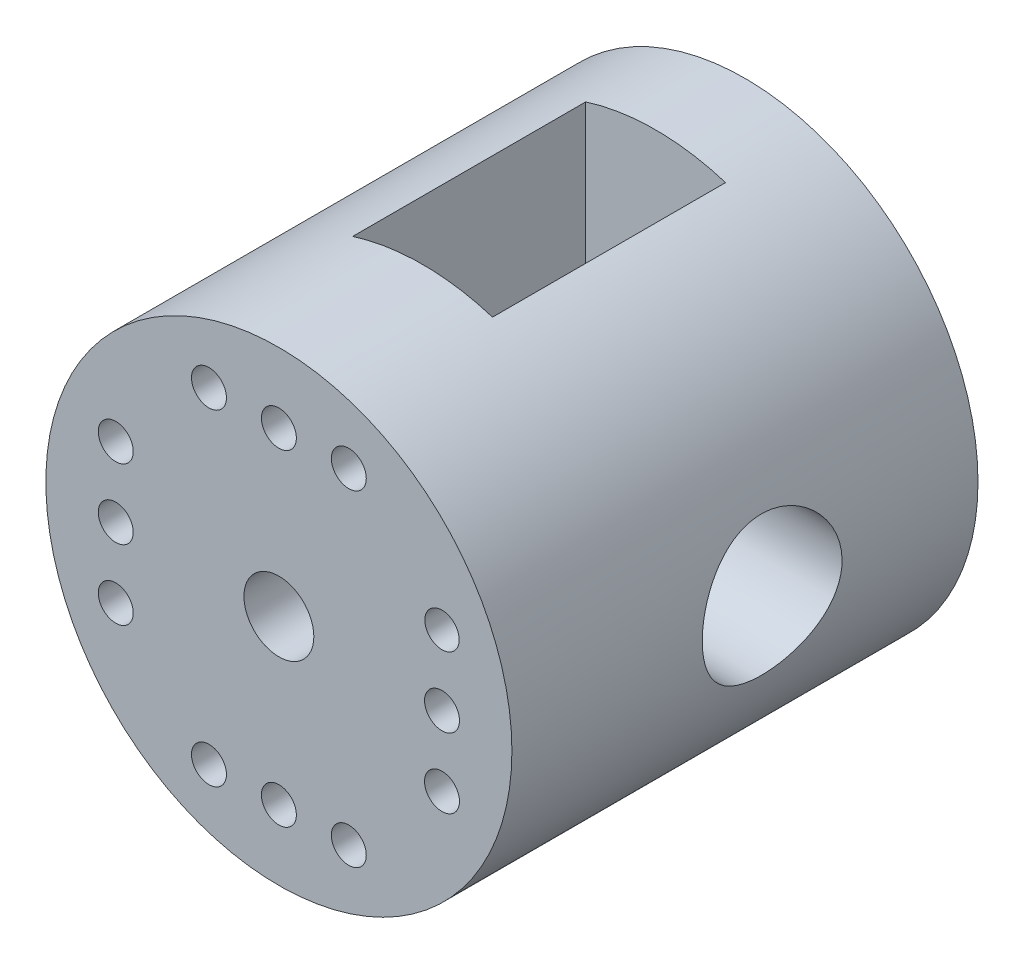
SolidWorks part; units mm, degrees
ref_plane "Front Plane" through (0, 0, 0) normal (0, 0, 1) x (1, 0, 0)
ref_plane "Top Plane" through (0, 0, 0) normal (0, 1, 0) x (1, 0, 0)
ref_plane "Right Plane" through (0, 0, 0) normal (1, 0, 0) x (0, 0, -1)
sketch "Sketch2" plane through (0, 0, 0) normal (0, 0, 1) x (1, 0, 0)
  circle A0 centre (0, 0) radius 1.5
  circle A1 centre (0, 0) radius 10
  circle A2 centre (7, 3) radius 0.7366
  circle A3 centre (7, 0) radius 0.75
  circle A4 centre (7, -3) radius 0.75
  circle A5 centre (3, -7) radius 0.75
  circle A6 centre (0, -7) radius 0.75
  circle A7 centre (-3, -7) radius 0.75
  circle A8 centre (-7, -3) radius 0.75
  circle A9 centre (-7, 0) radius 0.75
  circle A10 centre (-7, 3) radius 0.75
  circle A11 centre (-3, 7) radius 0.75
  circle A12 centre (0, 7) radius 0.75
  circle A13 centre (3, 7) radius 0.75
extrude "Boss-Extrude1" add sketch "Sketch2" along normal blind 5
sketch "Sketch3" plane through (0, 0, 0) normal (0, 0, 1) x (1, 0, 0)
  circle A0 centre (0, 0) radius 10
extrude "Boss-Extrude2" add sketch "Sketch3" against normal blind 15
sketch "Sketch4" plane through (0, 0, 0) normal (0, 1, 0) x (1, 0, 0)
  line L0 (-10, 15) -> (-10, 0) construction
  line L1 (-10, 15) -> (-10, -5) construction
  line L2 (-10, 0) -> (10, 0) construction
  line L3 (10, -5) -> (10, 15) construction
  line L5 (-3, 11.1675) -> (3, 11.1675)
  line L10 (-3, 11.1675) -> (-3, 1.1675)
  line L11 (-3, 1.1675) -> (3, 1.1675)
  line L12 (3, 11.1675) -> (3, 1.1675)
  line L13 (-3, 11.1675) -> (3, 1.1675) construction
  line L14 (-3, 1.1675) -> (3, 11.1675) construction
  point P5 (0, 6.1675)
  dimension "D1" = 6
  dimension "D2" = 10
extrude "Cut-Extrude1" cut sketch "Sketch4" against normal blind 20 and the other way blind 20
sketch "Sketch5" plane through (0, 0, 0) normal (1, 0, 0) x (0, 0, -1)
  line L0 (1.1675, 9.5394) -> (11.1675, -9.5394) construction
  circle A0 centre (6.1675, 0) radius 3
  dimension "D1" = 6
extrude "Cut-Extrude2" cut sketch "Sketch5" against normal blind 20 and the other way blind 20
